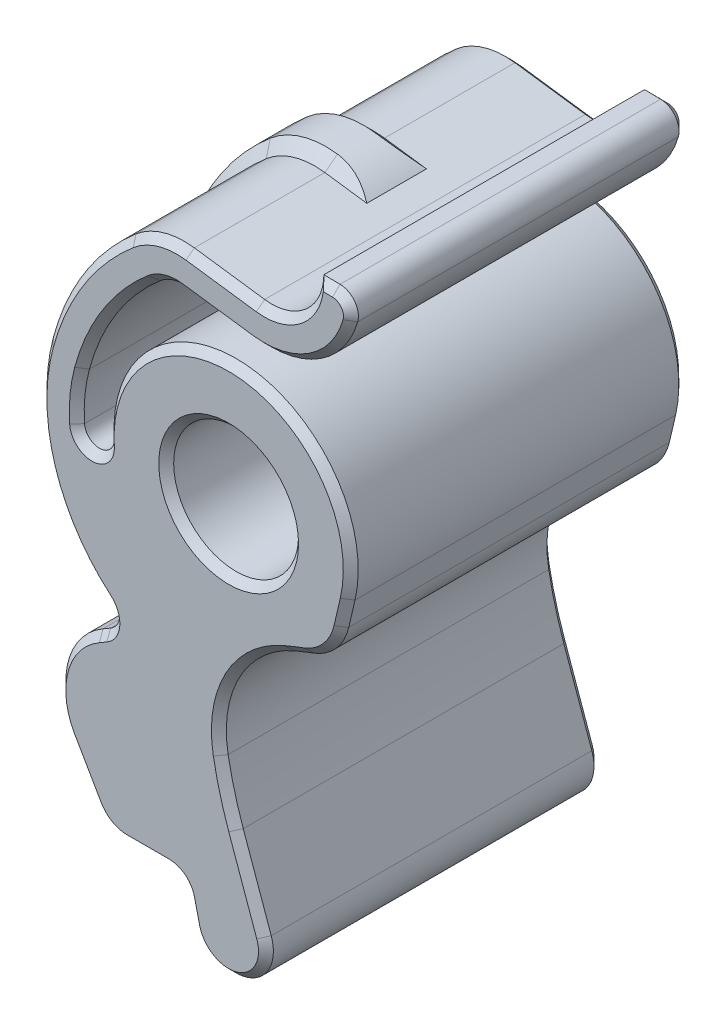
SolidWorks part; units mm, degrees
ref_plane "Front" through (0, 0, 0) normal (0, 0, 1) x (1, 0, 0)
ref_plane "Top" through (0, 0, 0) normal (0, 1, 0) x (1, 0, 0)
ref_plane "Right" through (0, 0, 0) normal (1, 0, 0) x (0, 0, -1)
sketch "Sketch1" plane through (0, 0, 0) normal (0, 0, 1) x (1, 0, 0)
  line L0 (-3.1891, -0.7451) -> (-0.9738, -10.2275)
  line L1 (0.9738, -10.2275) -> (3.1891, -0.7451)
  line L2 (0, 1.675) -> (0, 3.275) construction
  line L3 (0, -11) -> (0, 0) construction
  line L4 (0, 1.575) -> (0, 1.675) construction
  circle A0 centre (0, 0) radius 1.575 construction
  arc A1 (3.1891, -0.7451) -> (-3.1891, -0.7451) centre (0, 0) ccw
  arc A2 (-0.9738, -10.2275) -> (0.9738, -10.2275) centre (0, -10) ccw
  circle A5 centre (0, 0) radius 1.675
  dimension "D2" = 1
  dimension "D4" = 3.15
  dimension "D1" = 1.6
  dimension "D3" = 11
  dimension "D5" = 0.1
extrude "Boss-Extrude1" add sketch "Sketch1" along normal mid plane 10
sketch "Sketch2" plane through (0, 0, -5) normal (0, 0, -1) x (-1, 0, 0)
  line L2 (-3.1891, -0.7451) -> (-0.9738, -10.2275)
  line L3 (0.9738, -10.2275) -> (3.1891, -0.7451)
  line L4 (-3.1891, -0.7451) -> (-0.9738, -10.2275)
  line L5 (0.9738, -10.2275) -> (3.1891, -0.7451)
  arc A2 (3.1891, -0.7451) -> (-3.1891, -0.7451) centre (0, 0) ccw
  arc A3 (-0.9738, -10.2275) -> (0.9738, -10.2275) centre (0, -10) ccw
  arc A4 (3.1891, -0.7451) -> (-3.1891, -0.7451) centre (0, 0) ccw
  arc A5 (-0.9738, -10.2275) -> (0.9738, -10.2275) centre (0, -10) ccw
  dimension "D1" = 0
extrude "Movement Clearance" cut sketch "Sketch2" against normal blind 0.5
mirror "Movement Clearance 2" about plane through (0, 0, 0) normal (0, 0, 1) of "Movement Clearance"
sketch "Sketch6" plane through (0, 0, 0) normal (0, 0, 1) x (1, 0, 0)
  circle A7 centre (0, 0) radius 5.625 construction
  dimension "D3" = 11.25
sketch "Sketch19" plane through (0, 0, 0) normal (0, 0, 1) x (1, 0, 0)
  line L0 (-1.2013, -9.2537) -> (-2.7239, -9.2537)
  line L1 (-3.1891, -0.7451) -> (-0.9738, -10.2275) construction
  line L2 (-3.59, -8.7537) -> (-4.3013, -7.5217)
  line L3 (-3.5692, -4.7896) -> (-2.4017, -4.1155)
  line L4 (-2.4017, -4.1155) -> (-1.2013, -9.2537)
  line L5 (-0.9738, -10.2275) -> (-3.1891, -0.7451) construction
  arc A0 (-4.3013, -7.5217) -> (-3.5692, -4.7896) centre (-2.5692, -6.5217) cw
  arc A1 (-2.7239, -9.2537) -> (-3.59, -8.7537) centre (-2.7239, -8.2537) cw
  point P11 (-5.3013, -5.7896)
  point P14 (-3.3013, -9.2537)
  dimension "D5" = 2
  dimension "D6" = 1
  dimension "D1" = 1
  dimension "D2" = 60
  dimension "D3" = 4
  dimension "D4" = 2.1
extrude "Closed Stopper" add sketch "Sketch19" along normal through all and the other way through all
fillet "Fillet12" radius 0.5 2 edges at (-1.2013, -9.2537, 0) (-2.4017, -4.1155, 0)
sketch "Sketch14" plane through (0, 0, 0) normal (0, 0, 1) x (1, 0, 0)
  line L0 (0, 0) -> (0.7664, 5.0285) construction
  line L1 (0.9549, 6.4157) -> (0.7664, 5.0285) construction
  line L2 (0.9549, 6.4157) -> (2.3548, 6.3977) construction
  line L3 (-1.1196, 5.2847) -> (0.7664, 5.0285)
  line L4 (-2.723, -4.301) -> (-3.5692, -4.7896) construction
  line L5 (0, 0) -> (-4.9021, 1.3135) construction
  line L6 (0, 0) -> (-2.6882, 4.8234) construction
  line L7 (0, 0) -> (0, 3.275) construction
  line L8 (0, 0) -> (-1.778, 4.7533) construction
  line L9 (-1.778, 4.7533) -> (-1.9532, 5.2217) construction
  circle A0 centre (0, 0) radius 5.075 construction
  arc A2 (-2.7078, -4.2923) -> (-1.3348, -4.8963) centre (0, 0) ccw
  arc A5 (0.7664, 5.0285) -> (2.3548, 6.3977) centre (0.9549, 6.4157) ccw
  arc A6 (-2.7078, -4.2923) -> (-4.9021, 1.3135) centre (0, 0) cw
  arc A7 (-4.9021, 1.3135) -> (-2.6882, 4.8234) centre (1.8594, -0.4982) cw
  arc A8 (-2.6882, 4.8234) -> (-1.1196, 5.2847) centre (-1.3889, 3.3029) cw
  dimension "D3" = 2
  dimension "D9" = 1.4
  dimension "D4" = 75
  dimension "D10" = 97
  dimension "D2" = 0.5
  dimension "D1" = 10.15
  dimension "D5" = 1.5
  dimension "D8" = 7
extrude "Spring" add sketch "Sketch14" along normal through all and the other way through all thin thin type one direction wall 1
sketch "Sketch26" plane through (0, 0, 0) normal (0, 0, 1) x (1, 0, 0)
  line L2 (-3.1891, -0.7451) -> (-0.9738, -10.2275) construction
  line L3 (-3.1891, -0.7451) -> (-2.6375, -3.1063)
  arc A3 (-3.9361, 1.0547) -> (-2.6375, -3.1063) centre (0, 0) ccw construction
  arc A7 (-4.0659, -0.2717) -> (-2.6375, -3.1063) centre (0, 0) ccw
  arc A8 (-4.0659, -0.2717) -> (-3.2677, -0.2184) centre (-3.6668, -0.2451) ccw
  arc A9 (3.1891, -0.7451) -> (-3.1891, -0.7451) centre (0, 0) ccw construction
  arc A10 (-3.2677, -0.2184) -> (-3.1891, -0.7451) centre (0, 0) ccw
  dimension "D1" = 0.5
extrude "Spring Fillet 1a" add sketch "Sketch26" along normal through all and the other way through all
fillet "Spring Fillet 1" radius 0.5 1 edges at (-2.7081, -4.2921, 0)
fillet "Spring End Fillet" radius 0.5 1 edges at (3.3547, 6.3849, 0)
sketch "Sketch25" plane through (0, 0, 0) normal (0, 0, 1) x (1, 0, 0)
  line L5 (-1.1196, 5.2847) -> (0.7664, 5.0285) construction
  line L6 (0.8068, 5.3257) -> (-1.0792, 5.582)
  line L7 (-1.1196, 5.2847) -> (0.0058, 5.1318)
  arc A23 (-5.2509, 1.1482) -> (-4.2685, -2.7451) centre (-0.8548, 0.1869) ccw
  arc A24 (-4.9021, 1.3135) -> (-2.7078, -4.2923) centre (0, 0) ccw construction
  arc A25 (-1.1196, 5.2847) -> (-2.6882, 4.8234) centre (-1.3889, 3.3029) ccw construction
  arc A26 (-2.6882, 4.8234) -> (-4.9021, 1.3135) centre (1.8594, -0.4982) ccw construction
  arc A27 (-1.1196, 5.2847) -> (-2.6882, 4.8234) centre (-1.3889, 3.3029) ccw
  arc A28 (0.8068, 5.3257) -> (2.0548, 6.4016) centre (0.9549, 6.4157) ccw
  arc A29 (-1.0792, 5.582) -> (-2.8831, 5.0514) centre (-1.3889, 3.3029) ccw
  arc A30 (-2.8831, 5.0514) -> (-5.1919, 1.3912) centre (1.8594, -0.4982) ccw
  arc A31 (-5.1919, 1.3912) -> (-2.8678, -4.546) centre (0, 0) ccw
  arc A32 (-2.8678, -4.546) -> (-1.4137, -5.1858) centre (0, 0) ccw
  arc A33 (-4.9021, 1.3135) -> (-4.2685, -2.7451) centre (0, 0) ccw
  arc A34 (0.0058, 5.1318) -> (-2.8831, 5.0514) centre (-1.3889, 3.3029) ccw
  arc A35 (-2.8831, 5.0514) -> (-5.1919, 1.3912) centre (1.8594, -0.4982) ccw
  arc A36 (-5.1919, 1.3912) -> (-5.2509, 1.1482) centre (0, 0) ccw
  arc A37 (-2.6882, 4.8234) -> (-4.9021, 1.3135) centre (1.8594, -0.4982) ccw
  point P5 (-5.2972, 0.9112)
  point P10 (-4.6357, -2.0654)
  point P11 (-5.274, 1.0373)
  dimension "D2" = 4.5
  dimension "D3" = 0.25
  dimension "D1" = 0.3
extrude "Friction Rib" add sketch "Sketch25" along normal mid plane 1
chamfer "Friction Rib Chamfer" distance 0.3 angle 45 8 edges at (-5.0143, -0.7827, -0.5) (-1.9532, 5.2217, -0.5) (-4.0612, 3.2363, -0.5) (-5.0143, -0.7827, 0.5) (-1.9532, 5.2217, 0.5) (-4.0612, 3.2363, 0.5) (-0.5569, 5.2083, -0.5) (-0.5569, 5.2083, 0.5)
sketch "Sketch8" plane through (0, 0, 0) normal (0, 0, 1) x (1, 0, 0)
  line L0 (0.9422, -9.665) -> (0.1914, -7.5534)
  line L1 (3.1891, -0.7451) -> (0.9738, -10.2275) construction
  line L2 (3.0213, -1.4635) -> (0.9738, -10.2275)
  line L3 (1.5724, -2.7326) -> (-2.4836, -4.4418) construction
  arc A0 (0.9738, -10.2275) -> (0.9422, -9.665) centre (0, -10) ccw
  arc A6 (0.1914, -7.5534) -> (-0.214, -6.035) centre (9.378, -4.287) cw
  arc A7 (-0.214, -6.035) -> (1.5724, -2.7326) centre (2.7374, -5.4972) cw
  arc A8 (1.5724, -2.7326) -> (2.0912, -2.5253) centre (7.3972, -16.5555) cw
  arc A9 (2.0912, -2.5253) -> (3.0213, -1.4635) centre (1.5606, -1.1222) ccw
  point P16 (-1.4729, -5.1589)
  point P17 (1.0737, -3.3476)
  point P18 (-2.0845, -5.5848)
  point P19 (1.9093, -2.8256)
  point P21 (-0.1546, -5.9957)
  point P22 (2.0973, -2.523)
  dimension "D1" = 1.5
  dimension "D2" = 15
  dimension "D5" = 9
  dimension "D3" = 54
  dimension "D4" = 9.75
  dimension "D6" = 3
extrude "Clearance Cut" cut sketch "Sketch8" against normal through all both and the other way through all
chamfer "Chamfer2" distance 0.2 angle 45 34 edges at (-1.0424, -9.9337, -4.5) (0.2817, -10.9595, -4.5) (3.1052, -1.1043, -4.5) (0.2663, 3.2642, -4.5) (3.1052, -1.1043, 4.5) (0.2817, -10.9595, 4.5) (-1.0424, -9.9337, 4.5) (0.2663, 3.2642, 4.5) (-1.675, 0, -4.5) (1.675, 0, 4.5) (1.8308, -2.6265, -4.5) (0.0987, -4.0698, -4.5) (0.5668, -8.6092, -4.5) (0.0987, -4.0698, 4.5) (1.8308, -2.6265, 4.5) (0.5668, -8.6092, 4.5) (2.5712, 6.3949, -4.5) (2.5712, 6.3949, 4.5) (-3.469, -4.7318, -4.5) (-3.9456, -8.1377, -4.5) (-2.1609, -9.2537, -4.5) (-2.1609, -9.2537, 4.5) (-3.9456, -8.1377, 4.5) (-3.469, -4.7318, 4.5) (-4.5011, -6.004, -4.5) (-4.5011, -6.004, 4.5) (-3.2239, -9.1197, -4.5) (-1.2872, -9.362, -4.5) (-1.2872, -9.362, 4.5) (-3.2239, -9.1197, 4.5) (-0.3112, 4.1657, -4.5) (-0.1766, 5.1566, -4.5) (-0.1766, 5.1566, 4.5) (-0.3112, 4.1657, 4.5)
equation "\"D4@Sketch1\"=\"Hardware Clearance Hole Diameter@Box Assy.SLDASM\""
equation "\"D1@Boss-Extrude1\"=\"Hardware Length@Box Assy.Assembly\"/2"
